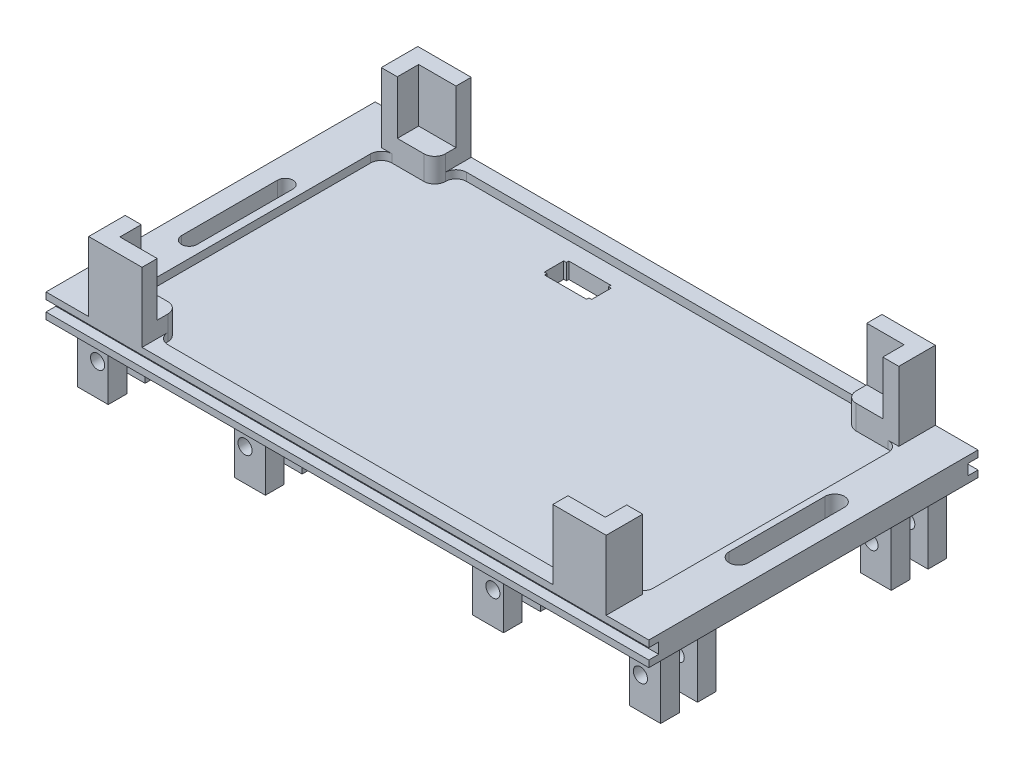
SolidWorks part; units mm, degrees
ref_plane "前视基准面" through (0, 0, 0) normal (0, 0, 1) x (1, 0, 0)
ref_plane "上视基准面" through (0, 0, 0) normal (0, 1, 0) x (1, 0, 0)
ref_plane "右视基准面" through (0, 0, 0) normal (1, 0, 0) x (0, 0, -1)
other "Configuration Table"
sketch "草图1" plane through (0, 0, 0) normal (0, 1, 0) x (1, 0, 0)
  line L1 (-90, -45) -> (90, -45)
  line L2 (-90, -45) -> (-90, 45)
  line L3 (-90, 45) -> (90, 45)
  line L4 (90, -45) -> (90, 45)
  line L5 (-90, -45) -> (90, 45) construction
  line L6 (-90, 45) -> (90, -45) construction
  point P0 (0, 0)
  dimension "D1" = 90
  dimension "D2" = 180
extrude "凸台-拉伸1" add sketch "草图1" along normal blind 4.5
sketch "草图2" plane through (0, 4.5, 0) normal (0, 1, 0) x (1, 0, 0)
  line L0 (0, 0) -> (50000, 0) construction
  line L1 (-45.5, -28) -> (45.5, -28) construction
  line L2 (-45.5, -28) -> (-45.5, 28) construction
  line L3 (-45.5, 28) -> (45.5, 28) construction
  line L4 (45.5, -28) -> (45.5, 28) construction
  line L5 (-45.5, -28) -> (45.5, 28) construction
  line L6 (-45.5, 28) -> (45.5, -28) construction
  line L7 (38.5, 24) -> (48.5, 24)
  line L8 (38.5, 24) -> (38.5, 31)
  line L9 (38.5, 31) -> (48.5, 31)
  line L10 (48.5, 24) -> (48.5, 31)
  line L11 (38.5, 24) -> (48.5, 31) construction
  line L12 (38.5, 31) -> (48.5, 24) construction
  line L13 (0, 0) -> (0, 50000) construction
  line L14 (-38.5, 31) -> (-48.5, 31)
  line L15 (-48.5, 24) -> (-48.5, 31)
  line L16 (-38.5, 24) -> (-48.5, 24)
  line L17 (-38.5, 24) -> (-38.5, 31)
  line L18 (-38.5, -24) -> (-38.5, -31)
  line L19 (-38.5, -24) -> (-48.5, -24)
  line L20 (-48.5, -24) -> (-48.5, -31)
  line L21 (-38.5, -31) -> (-48.5, -31)
  line L22 (38.5, -31) -> (48.5, -31)
  line L23 (48.5, -24) -> (48.5, -31)
  line L24 (38.5, -24) -> (48.5, -24)
  line L25 (38.5, -24) -> (38.5, -31)
  point P0 (0, 0)
  dimension "D1" = 56
  dimension "D2" = 91
  dimension "D3" = 10
  dimension "D4" = 7
  dimension "D5" = 3
  dimension "D6" = 3
extrude "凸台-拉伸2" add sketch "草图2" along normal blind 3
sketch "草图3" plane through (0, 7.5, 0) normal (0, 1, 0) x (1, 0, 0)
  line L0 (-48.5, 31) -> (-48.5, 24)
  line L1 (-48.5, 24) -> (-45.5, 24)
  line L2 (-38.5, 24) -> (-48.5, 24) construction
  line L3 (-45.5, -28) -> (-45.5, 28) construction
  line L4 (-45.5, 24) -> (-45.5, 28)
  line L5 (-45.5, 28) -> (-38.5, 28)
  line L6 (-38.5, 24) -> (-38.5, 31) construction
  line L7 (-45.5, 28) -> (45.5, 28) construction
  line L8 (-38.5, 28) -> (-38.5, 31)
  line L9 (-38.5, 31) -> (-48.5, 31)
  line L10 (0, 0) -> (0, 48678.4952) construction
  line L11 (-45.5, 28) -> (45.5, -28) construction
  line L13 (0, 0) -> (50000, 0) construction
  line L15 (38.5, 28) -> (38.5, 31)
  line L16 (45.5, 28) -> (38.5, 28)
  line L17 (45.5, 24) -> (45.5, 28)
  line L18 (48.5, 24) -> (45.5, 24)
  line L19 (48.5, 31) -> (48.5, 24)
  line L20 (38.5, 31) -> (48.5, 31)
  line L21 (38.5, -31) -> (48.5, -31)
  line L22 (48.5, -31) -> (48.5, -24)
  line L23 (48.5, -24) -> (45.5, -24)
  line L24 (45.5, -24) -> (45.5, -28)
  line L25 (45.5, -28) -> (38.5, -28)
  line L26 (38.5, -28) -> (38.5, -31)
  line L27 (-38.5, -28) -> (-38.5, -31)
  line L28 (-45.5, -28) -> (-38.5, -28)
  line L29 (-45.5, -24) -> (-45.5, -28)
  line L30 (-48.5, -24) -> (-45.5, -24)
  line L31 (-48.5, -31) -> (-48.5, -24)
  line L32 (-38.5, -31) -> (-48.5, -31)
  point P22 (0, 0)
extrude "凸台-拉伸3" add sketch "草图3" along normal blind 10
sketch "草图9" plane through (0, 4.5, 0) normal (0, 1, 0) x (1, 0, 0)
  line L1 (-48.5, 31) -> (48.5, 31)
  line L2 (-48.5, 31) -> (-48.5, -31)
  line L3 (-48.5, -31) -> (48.5, -31)
  line L4 (48.5, 31) -> (48.5, -31)
  line L5 (-90, 45) -> (90, 45)
  line L6 (-90, 45) -> (-90, -45)
  line L7 (-90, -45) -> (90, -45)
  line L8 (90, 45) -> (90, -45)
extrude "切除-拉伸3" cut sketch "草图9" against normal blind 13
sketch "草图10" plane through (0, 4.5, 0) normal (0, 1, 0) x (1, 0, 0)
  line L0 (-48.5, 31) -> (-48.5, 24) construction
  line L1 (-48.5, 31) -> (-56.5, 31)
  line L2 (-48.5, 31) -> (-48.5, -31)
  line L3 (-48.5, -31) -> (-56.5, -31)
  line L4 (-56.5, 31) -> (-56.5, -31)
  line L5 (-38.5, 31) -> (-48.5, 31) construction
  line L6 (48.5, 24) -> (48.5, 31) construction
  line L7 (48.5, 31) -> (56.5, 31)
  line L8 (48.5, 31) -> (48.5, -31)
  line L9 (48.5, -31) -> (56.5, -31)
  line L10 (56.5, 31) -> (56.5, -31)
  line L11 (48.5, 31) -> (38.5, 31) construction
  line L12 (-38.5, -31) -> (38.5, -31) construction
  line L13 (-56.5, 0) -> (49943.5, 0) construction
  line L14 (51.5, 9) -> (51.5, -9) construction
  line L15 (52.95, 9) -> (52.95, -9)
  line L16 (50.05, 9) -> (50.05, -9)
  line L17 (0, 0) -> (0, 17.5) construction
  line L18 (-51.5, 9) -> (-51.5, -9) construction
  line L19 (-52.95, 9) -> (-52.95, -9)
  line L20 (-50.05, 9) -> (-50.05, -9)
  arc A0 (52.95, 9) -> (50.05, 9) centre (51.5, 9) ccw
  arc A1 (50.05, -9) -> (52.95, -9) centre (51.5, -9) ccw
  arc A2 (-52.95, 9) -> (-50.05, 9) centre (-51.5, 9) cw
  arc A3 (-50.05, -9) -> (-52.95, -9) centre (-51.5, -9) cw
  point P20 (-56.5, 0)
  point P23 (51.5, 0)
  point P32 (-51.5, 0)
  dimension "D1" = 8
  dimension "D2" = 8
  dimension "D3" = 2.9
  dimension "D4" = 18
  dimension "D5" = 5
  dimension "D6" = 5
extrude "凸台-拉伸5" add sketch "草图10" against normal blind 4.5
sketch "草图11" plane through (0, 0, 0) normal (0, -1, 0) x (1, 0, 0)
  line L0 (48.55, 2) -> (25.55, 2) construction
  line L1 (48.875, 19.9092) -> (54.675, 19.9092)
  line L2 (48.875, 19.9092) -> (48.875, 16.4092)
  line L3 (48.875, 16.4092) -> (54.675, 16.4092)
  line L4 (54.675, 19.9092) -> (54.675, 16.4092)
  line L5 (48.875, 23.3092) -> (54.675, 23.3092)
  line L6 (48.875, 23.3092) -> (48.875, 26.8092)
  line L7 (48.875, 26.8092) -> (54.675, 26.8092)
  line L8 (54.675, 23.3092) -> (54.675, 26.8092)
  line L9 (37.05, 2) -> (37.05, 22.7385) construction
  line L10 (25.225, 26.8092) -> (19.425, 26.8092)
  line L11 (19.425, 23.3092) -> (19.425, 26.8092)
  line L12 (25.225, 23.3092) -> (19.425, 23.3092)
  line L13 (25.225, 23.3092) -> (25.225, 26.8092)
  line L14 (25.225, 16.4092) -> (19.425, 16.4092)
  line L15 (19.425, 19.9092) -> (19.425, 16.4092)
  line L16 (25.225, 19.9092) -> (19.425, 19.9092)
  line L17 (25.225, 19.9092) -> (25.225, 16.4092)
  dimension "D1" = 3.5
  dimension "D2" = 3.4
  dimension "D3" = 3.5
  dimension "D4" = 5.8
  dimension "D5" = 5.8
  dimension "D6" = 23.65
extrude "凸台-拉伸6" add sketch "草图11" along normal blind 12
sketch "草图12" plane through (0, 0, 26.8092) normal (0, 0, 1) x (1, 0, 0)
  circle A0 centre (50.875, -6) radius 1.325
  circle A1 centre (23.225, -6) radius 1.325
  dimension "D1" = 2.65
  dimension "D2" = 2.65
extrude "切除-拉伸4" cut sketch "草图12" against normal through all
mirror "镜向4" about plane through (0, 0, 0) normal (1, 0, 0) of "切除-拉伸4", "凸台-拉伸6" second plane through (0, 0, 0) second plane normal (0, 0, 1)
sketch "草图13" plane through (0, 0, 0) normal (0, -1, 0) x (1, 0, 0)
  line L0 (52.95, 9) -> (52.95, -9) construction
  line L1 (52.95, 9) -> (52.95, -9)
  line L2 (50.05, -9) -> (50.05, 9) construction
  line L3 (50.05, -9) -> (50.05, 9)
  line L4 (53.3, 9) -> (53.3, -9)
  line L5 (49.7, -9) -> (49.7, 9)
  arc A0 (50.05, -9) -> (52.95, -9) centre (51.5, -9) ccw construction
  arc A1 (50.05, -9) -> (52.95, -9) centre (51.5, -9) ccw
  arc A2 (52.95, 9) -> (50.05, 9) centre (51.5, 9) ccw construction
  arc A3 (52.95, 9) -> (50.05, 9) centre (51.5, 9) ccw
  arc A4 (49.7, -9) -> (53.3, -9) centre (51.5, -9) ccw
  arc A5 (53.3, 9) -> (49.7, 9) centre (51.5, 9) ccw
  dimension "D1" = 0.35
extrude "切除-拉伸5" cut sketch "草图13" against normal blind 8
sketch "草图14" plane through (0, 0, 0) normal (0, -1, 0) x (1, 0, 0)
  line L0 (-52.95, -9) -> (-52.95, -6)
  line L1 (-52.95, -9) -> (-52.95, 9) construction
  line L2 (-52.95, -6) -> (-50.05, -6)
  line L3 (-50.05, 9) -> (-50.05, -9) construction
  line L4 (-50.05, -6) -> (-50.05, -9)
  line L5 (-52.95, 9) -> (-52.95, 6)
  line L6 (-52.95, 6) -> (-50.05, 6)
  line L7 (-50.05, 6) -> (-50.05, 9)
  arc A0 (-52.95, 9) -> (-50.05, 9) centre (-51.5, 9) ccw
  arc A1 (-50.05, -9) -> (-52.95, -9) centre (-51.5, -9) ccw
  dimension "D1" = 3
  dimension "D2" = 3
sketch "草图15" plane through (56.5, 0, 0) normal (1, 0, 0) x (0, 0, -1)
  line L0 (-31, 4.5) -> (-29, 4.5) construction
  line L1 (-31, 4.5) -> (31, 4.5) construction
  line L2 (-29, 4.5) -> (-29, 3.25) construction
  line L3 (-31, 0) -> (31, 0) construction
  line L4 (-29, 0) -> (-31, 0) construction
  line L5 (-31, 0) -> (-31, 1.25) construction
  line L6 (-31, 0) -> (-31, 4.5) construction
  line L7 (-31, 1.25) -> (-29, 1.25)
  line L8 (-31, 4.5) -> (-31, 3.25) construction
  line L9 (-31, 3.25) -> (-29, 3.25)
  line L10 (0, 0) -> (0, 50000) construction
  line L11 (-29, 1.25) -> (-29, 0) construction
  line L12 (29, 1.25) -> (29, 0) construction
  line L13 (31, 3.25) -> (29, 3.25)
  line L14 (31, 4.5) -> (31, 3.25) construction
  line L15 (31, 1.25) -> (29, 1.25)
  line L16 (31, 0) -> (31, 1.25) construction
  line L17 (29, 0) -> (31, 0) construction
  line L18 (29, 4.5) -> (29, 3.25) construction
  line L19 (31, 4.5) -> (29, 4.5) construction
  line L20 (29, 3.25) -> (29, 1.25)
  line L21 (31, 3.25) -> (31, 1.25)
  line L22 (-29, 3.25) -> (-29, 1.25)
  line L23 (-31, 3.25) -> (-31, 1.25)
  dimension "D1" = 2
  dimension "D2" = 2
extrude "切除-拉伸6" cut sketch "草图15" against normal through all
sketch "草图16" plane through (0, 0, 0) normal (0, -1, 0) x (1, 0, 0)
  line L0 (56.5, 31) -> (56.5, -31) construction
  line L1 (-56.5, 31) -> (56.5, 31)
  line L2 (-56.5, 31) -> (-56.5, 30.85)
  line L3 (-56.5, 30.85) -> (56.5, 30.85)
  line L4 (56.5, 31) -> (56.5, 30.85)
  line L5 (-56.5, -31) -> (-56.5, 31) construction
  line L6 (56.5, -31) -> (-56.5, -31)
  line L7 (56.5, -31) -> (56.5, -30.85)
  line L8 (56.5, -30.85) -> (-56.5, -30.85)
  line L9 (-56.5, -31) -> (-56.5, -30.85)
  dimension "D1" = 0.15
  dimension "D2" = 0.15
extrude "切除-拉伸7" cut sketch "草图16" against normal through all
sketch "草图17" plane through (0, 0, 0) normal (0, -1, 0) x (1, 0, 0)
  line L0 (-6.2973, -24.5179) -> (-6.2973, -24.0625)
  line L1 (-6.2973, -24.0625) -> (-5.7913, -24.0625)
  line L2 (-5.7913, -24.0625) -> (-5.7913, -20.7229)
  line L3 (-5.7913, -20.7229) -> (-6.2973, -20.7229)
  line L4 (-6.2973, -20.7229) -> (-6.2973, -20.2675)
  line L5 (-6.2973, -20.2675) -> (-13.862, -20.2675)
  line L6 (-13.862, -20.2675) -> (-13.862, -20.7229)
  line L7 (-13.862, -20.7229) -> (-14.368, -20.7229)
  line L8 (-14.368, -20.7229) -> (-14.368, -24.0625)
  line L9 (-14.368, -24.0625) -> (-13.862, -24.0625)
  line L10 (-13.862, -24.0625) -> (-13.862, -24.5179)
  line L11 (-13.862, -24.5179) -> (-6.2973, -24.5179)
extrude "切除-拉伸8" cut sketch "草图17" against normal blind 10
sketch "草图18" plane through (0, 0, 0) normal (0, -1, 0) x (1, 0, 0)
  line L0 (-14.368, -20.7229) -> (-14.368, -24.0625) construction
  line L1 (-6.2973, -20.2675) -> (-13.862, -20.2675) construction
  line L2 (-13.862, -20.2675) -> (-13.862, -20.7229) construction
  line L3 (-13.862, -20.7229) -> (-14.368, -20.7229) construction
  line L4 (-14.368, -24.0625) -> (-13.862, -24.0625) construction
  line L5 (-13.862, -24.0625) -> (-13.862, -24.5179) construction
  line L6 (-13.862, -24.5179) -> (-6.2973, -24.5179) construction
  line L7 (-6.2973, -24.5179) -> (-6.2973, -24.0625) construction
  line L8 (-6.2973, -24.0625) -> (-5.7913, -24.0625) construction
  line L9 (-5.7913, -24.0625) -> (-5.7913, -20.7229) construction
  line L10 (-14.368, -20.7229) -> (-14.368, -24.0625)
  line L11 (-6.2973, -20.2675) -> (-13.862, -20.2675)
  line L12 (-13.862, -20.2675) -> (-13.862, -20.7229)
  line L13 (-13.862, -20.7229) -> (-14.368, -20.7229)
  line L14 (-14.368, -24.0625) -> (-13.862, -24.0625)
  line L15 (-13.862, -24.0625) -> (-13.862, -24.5179)
  line L16 (-13.862, -24.5179) -> (-6.2973, -24.5179)
  line L17 (-6.2973, -24.5179) -> (-6.2973, -24.0625)
  line L18 (-6.2973, -24.0625) -> (-5.7913, -24.0625)
  line L19 (-5.7913, -24.0625) -> (-5.7913, -20.7229)
  line L20 (-6.2973, -20.2675) -> (-6.2973, -20.7229)
  line L21 (-6.2973, -20.7229) -> (-5.7913, -20.7229)
  line L22 (-6.1473, -20.5729) -> (-5.6413, -20.5729)
  line L23 (-5.6413, -24.2125) -> (-5.6413, -20.5729)
  line L24 (-6.1473, -24.2125) -> (-5.6413, -24.2125)
  line L25 (-6.1473, -24.6679) -> (-6.1473, -24.2125)
  line L26 (-14.012, -24.6679) -> (-6.1473, -24.6679)
  line L27 (-14.012, -24.2125) -> (-14.012, -24.6679)
  line L28 (-14.518, -24.2125) -> (-14.012, -24.2125)
  line L29 (-14.518, -20.5729) -> (-14.518, -24.2125)
  line L30 (-14.012, -20.5729) -> (-14.518, -20.5729)
  line L31 (-14.012, -20.1175) -> (-14.012, -20.5729)
  line L32 (-6.1473, -20.1175) -> (-14.012, -20.1175)
  line L33 (-6.1473, -20.1175) -> (-6.1473, -20.5729)
  dimension "D1" = 0.15
extrude "切除-拉伸9" cut sketch "草图18" against normal blind 10
sketch "草图19" plane through (0, 4.5, 0) normal (0, 1, 0) x (1, 0, 0)
  line L0 (48.5, 24) -> (48.5, -24)
  line L2 (-48.5, -24) -> (-48.5, 24)
  line L3 (-48.5, 24) -> (-38.5, 24)
  line L4 (-38.5, 24) -> (-38.5, 28)
  line L5 (-38.5, 28) -> (38.5, 28)
  line L6 (38.5, 28) -> (38.5, 24)
  line L7 (38.5, 24) -> (48.5, 24)
  line L8 (48.5, -24) -> (38.5, -24)
  line L9 (38.5, -24) -> (38.5, -28)
  line L10 (38.5, -28) -> (-38.5, -28)
  line L11 (-38.5, -28) -> (-38.5, -24)
  line L12 (-38.5, -24) -> (-48.5, -24)
extrude "切除-拉伸10" cut sketch "草图19" against normal blind 1.5
fillet "圆角1" radius 2 12 edges at (48.5, 3.75, -24) (48.5, 3.75, 24) (38.5, 5.25, 24) (38.5, 3.75, 28) (-38.5, 5.25, 24) (-48.5, 3.75, -24) (-38.5, 5.25, -24) (-38.5, 3.75, -28) (38.5, 3.75, -28) (38.5, 5.25, -24) (-38.5, 3.75, 28) (-48.5, 3.75, 24)
